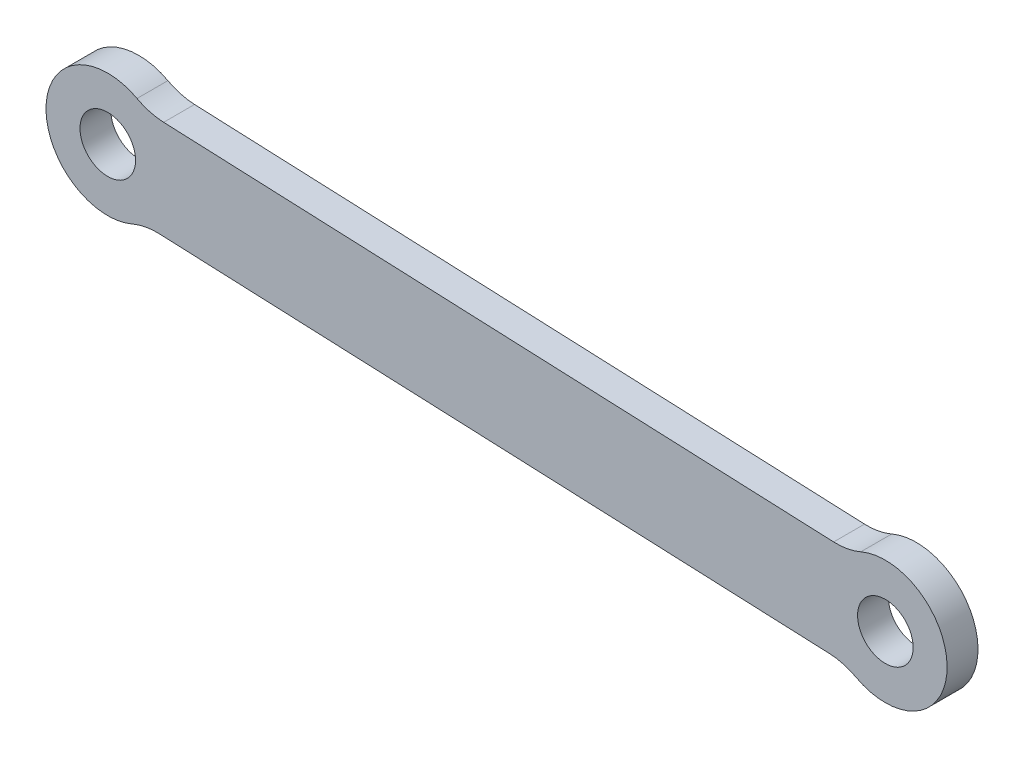
SolidWorks part; units mm, degrees
material "Thornel Mat VMA"
ref_plane "前视基准面" through (0, 0, 0) normal (0, 0, 1) x (1, 0, 0)
ref_plane "上视基准面" through (0, 0, 0) normal (0, 1, 0) x (1, 0, 0)
ref_plane "右视基准面" through (0, 0, 0) normal (1, 0, 0) x (0, 0, -1)
sketch "草图1" plane through (0, 0, 0) normal (0, 0, 1) x (1, 0, 0)
  line L0 (150.978, 33.8432) -> (276.8647, 28.5029) construction
  line L1 (151.317, 41.8361) -> (277.2038, 36.4957)
  line L2 (150.6389, 25.8504) -> (276.5257, 20.5101)
  arc A0 (151.317, 41.8361) -> (150.6389, 25.8504) centre (150.978, 33.8432) ccw
  arc A1 (276.5257, 20.5101) -> (277.2038, 36.4957) centre (276.8647, 28.5029) ccw
  circle A2 centre (150.978, 33.8432) radius 4.5
  circle A3 centre (276.8647, 28.5029) radius 4.5
  point P3 (213.9214, 31.1731)
  dimension "D1" = 9
  dimension "D2" = 9
  dimension "D3" = 8
  dimension "D4" = 126
extrude "凸台-拉伸1" add sketch "草图1" along normal blind 5
sketch "草图2" plane through (0, 0, 5) normal (0, 0, 1) x (1, 0, 0)
  circle A0 centre (150.978, 33.8432) radius 10
  circle A1 centre (276.8647, 28.5029) radius 10
  circle A2 centre (150.978, 33.8432) radius 4.5
  circle A3 centre (276.8647, 28.5029) radius 4.5
  dimension "D1" = 20
  dimension "D2" = 20
extrude "凸台-拉伸2" add sketch "草图2" against normal up to vertex (5 mm away) up to point (151.317, 41.8361, 0)
fillet "圆角1" radius 10 4 edges at (157.3116, 41.5818, 2.5) (156.6335, 25.5961, 2.5) (270.5311, 20.7644, 2.5) (271.2092, 36.75, 2.5)
